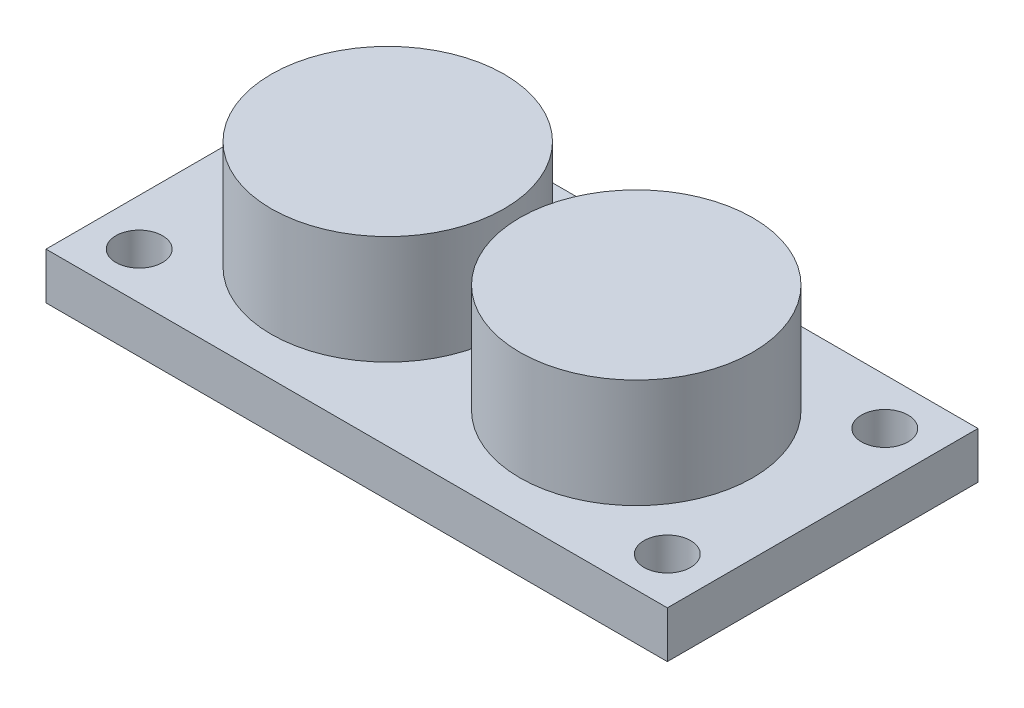
SolidWorks part; units mm, degrees
ref_plane "Front Plane" through (0, 0, 0) normal (0, 0, 1) x (1, 0, 0)
ref_plane "Top Plane" through (0, 0, 0) normal (0, 1, 0) x (1, 0, 0)
ref_plane "Right Plane" through (0, 0, 0) normal (1, 0, 0) x (0, 0, -1)
sketch "Sketch1" plane through (0, 0, 0) normal (0, 1, 0) x (1, 0, 0)
  line L0 (-0.4515, 8.8488) -> (-0.4515, -11.1512) construction
  line L1 (-20.4515, 8.8488) -> (19.5485, 8.8488)
  line L2 (-20.4515, 8.8488) -> (-20.4515, -11.1512)
  line L3 (-20.4515, -11.1512) -> (19.5485, -11.1512)
  line L4 (19.5485, 8.8488) -> (19.5485, -11.1512)
  circle A0 centre (-17.4515, 5.8488) radius 1.5
  circle A1 centre (-17.4515, -8.1512) radius 1.5
  circle A2 centre (-8.4515, -1.1512) radius 7.5
  circle A3 centre (16.5485, -8.1512) radius 1.5
  circle A4 centre (16.5485, 5.8488) radius 1.5
  circle A5 centre (7.5485, -1.1512) radius 7.5
  dimension "D3" = 3
  dimension "D4" = 3
  dimension "D7" = 3
  dimension "D9" = 15
  dimension "D1" = 40
  dimension "D2" = 20
  dimension "D5" = 3
  dimension "D6" = 3
  dimension "D8" = 3
  dimension "D10" = 10
  dimension "D11" = 12
extrude "Boss-Extrude1" add sketch "Sketch1" along normal blind 3
extrude "Boss-Extrude2" add sketch "Sketch1<2>" along normal blind 10 contours A2 | A5 region at (-8.4515, 0, 1.1512) region at (7.5485, 0, 1.1512)
sketch "Sketch1<2>" plane through (0, 0, 0) normal (0, 1, 0) x (1, 0, 0) same geometry as "Sketch1"
